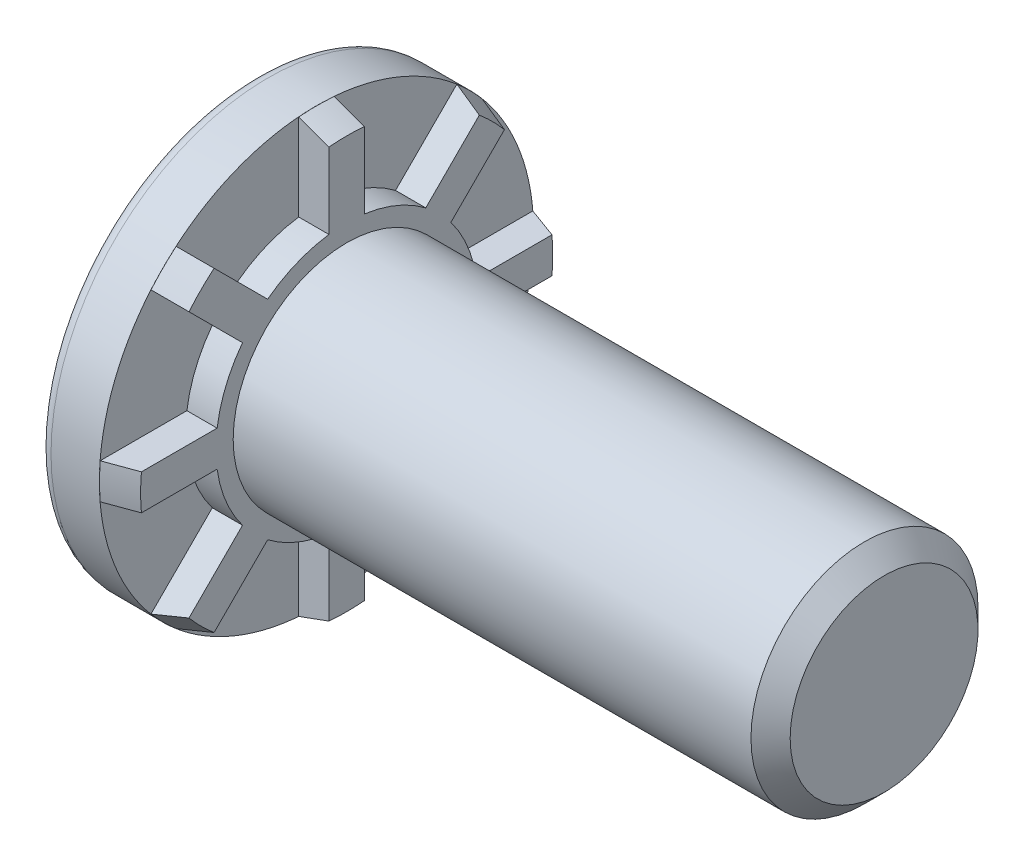
SolidWorks part; units mm, degrees
revolve "BaseBody" add sketch "BodySke" angle 360 about L6 other way angle 7.5
sketch "BodySke" plane through (0, 0, 0) normal (0, 0, 1) x (1, 0, 0)
  line L0 (-2.13, 7.224) -> (-2.13, 0)
  line L1 (1.065, 7.2608) -> (1.065, 4)
  line L2 (0.0025, 7.6475) -> (1.065, 7.2608)
  line L3 (1.065, 4) -> (19.3095, 4)
  line L4 (20, 3.3095) -> (20, 0)
  line L5 (20, 0) -> (-2.13, 0)
  line L6 (0, 0) -> (50.554, 0) construction
  line L8 (20, 3.3095) -> (19.3095, 4)
  line L9 (-1.704, 7.65) -> (0, 7.65)
  line L10 (0.0025, 7.6475) -> (0, 7.6475)
  line L11 (1.25, 19.05) -> (1.25, -3.175) construction
  line L12 (0, 7.6475) -> (0, 7.65)
  arc A0 (-2.13, 7.224) -> (-1.704, 7.65) centre (-1.704, 7.224) cw
  dimension "Fillet_rad" = 0.426
  dimension "Minor_dia" = 6.619
  dimension "Diameter" = 8
  dimension "T_dim" = 2.13
  dimension "H_dia" = 15.3
  dimension "D2" = 0.0025
  dimension "D3" = 0.0025
  dimension "Length" = 20
  dimension "Advance" = 1.25
  dimension "D1" = 20
cosmetic thread "ThreadCosmetic" [suppressed] parameters "Thread_length"=16.7, "Thread_minor"=6.619
ref_plane "Plane1" through (0, 0, 0) normal (0, 0, 1) x (1, 0, 0)
ref_plane "Plane2" through (0, 0, 0) normal (0, 1, 0) x (1, 0, 0)
ref_plane "Plane3" through (0, 0, 0) normal (1, 0, 0) x (0, 0, -1)
sketch "ThdSchSke" plane through (0, 0, 0) normal (0, 0, 1) x (1, 0, 0)
  line L0 (3.3, -3.3095) -> (2.8165, -4)
  line L1 (3.3, -3.3095) -> (3.7835, -4)
  line L2 (3.7835, -4) -> (3.7835, -5)
  line L3 (-3.175, 0) -> (5.1513, 0) construction
  line L4 (0, -7.65) -> (0, 7.65) construction
  line L5 (3.7835, -5) -> (2.8165, -5)
  line L6 (2.8165, -5) -> (2.8165, -4)
  dimension "Diameter" = 8
  dimension "Thread_minor" = 6.619
  dimension "Start" = 3.3
revolve "ThreadSchematic" [suppressed] cut sketch "ThdSchSke" angle 360 about L3
pattern_linear "ThdSchPat" [suppressed]
sketch "RibCutSke" plane through (1.065, 1.7944, -0.091) normal (1, 0, 0) x (0, 0, -1)
  line L0 (0.5348, 2.7713) -> (0.5348, 5.83)
  line L1 (2.695, 1.8765) -> (4.8578, 4.0393)
  line L2 (0.5348, 2.1564) -> (0.5348, 2.4006) construction
  line L3 (-0.091, -1.7944) -> (-0.091, 5.0239) construction
  line L4 (-0.091, -1.7944) -> (0.5348, 2.1564) construction
  line L5 (-0.091, -1.7944) -> (2.2602, 1.4417) construction
  line L6 (2.2602, 1.4417) -> (2.4379, 1.6194) construction
  arc A1 (2.695, 1.8765) -> (0.5348, 2.7713) centre (-0.091, -1.7944) ccw
  arc A2 (4.8578, 4.0393) -> (0.5348, 5.83) centre (-0.091, -1.7944) ccw
  circle A3 centre (-0.091, -1.7944) radius 7.2608 construction
  circle A4 centre (-0.091, -1.7944) radius 4 construction
  dimension "Rib_root_half_angle" = 9
  dimension "Rib_root_gap_angle" = 27
  dimension "Angle" = 45
extrude "RibCut" cut sketch "RibCutSke" against normal blind 1.065
pattern_circular "RibCutsPat" count 8 every 45 about axis through (0, 0, 0) along (1, 0, 0) of "RibCut"
equation "' \"Length@BodySke\" = 20"
equation "' \"H_dia@BodySke\" = 15.3"
equation "' \"Start@ThdSchSke\" = 3.3"
equation "' \"T_dim@BodySke\" = 2.13"
equation "' \"Diameter@BodySke\" = 8"
equation "' \"Minor_dia@BodySke\" = 6.619"
equation "' \"Advance@BodySke\" = 1.25"
equation "\"Fillet_rad@BodySke\" =  \"T_dim@BodySke\" * 0.2"
equation "\"Clinch_ht@BodySke\" = \"T_dim@BodySke\" * 0.5"
equation "\"Num_ribs@RibCutsPat\" = 8"
equation "\"Angle@RibCutSke\" =\"Angle@RibCutsPat\""
equation "\"Rib_root_half_angle@RibCutSke\" = \"Angle@RibCutSke\" / 5"
equation "\"Rib_root_gap_angle@RibCutSke\" = \"Angle@RibCutSke\" - (2 * \"Rib_root_half_angle@RibCutSke\" )"
equation "\"Rib_root_dia@RibCutSke\" = \"Diameter@BodySke\""
equation "\"Inner_dia@RibCutSke\" = \"Diameter@BodySke\" + ( \"H_dia@BodySke\" - \"Diameter@BodySke\" ) / 6"
equation "\"Outer_dia@RibCutSke\" = \"H_dia@BodySke\""
equation "\"Depth@RibCut\" = \"Clinch_ht@BodySke\""
equation "\"Thread_length@ThreadCosmetic\" = \"Length@BodySke\" - \"Start@ThdSchSke\""
equation "\"Thread_minor@ThreadCosmetic\" = \"Minor_dia@BodySke\""
equation "\"Thread_minor@ThdSchSke\" = \"Minor_dia@BodySke\""
equation "\"Diameter@ThdSchSke\" = \"Diameter@BodySke\""
equation "\"Overcut@ThdSchSke\" = \"Diameter@BodySke\" * 1.25"
equation "\"Num_threads@ThdSchPat\" = int( \"Thread_length@ThreadCosmetic\" / \"Advance@BodySke\" + 0.999 )  + 1"
equation "\"Advance@ThdSchPat\" = \"Thread_length@ThreadCosmetic\" /  (\"Num_threads@ThdSchPat\" - 1) 'relax it"
equation "\"Num_threads@ThdSchPat\" = \"Num_threads@ThdSchPat\" - sgn( \"Num_threads@ThdSchPat\" - 1) '---chamfered tips only---"
